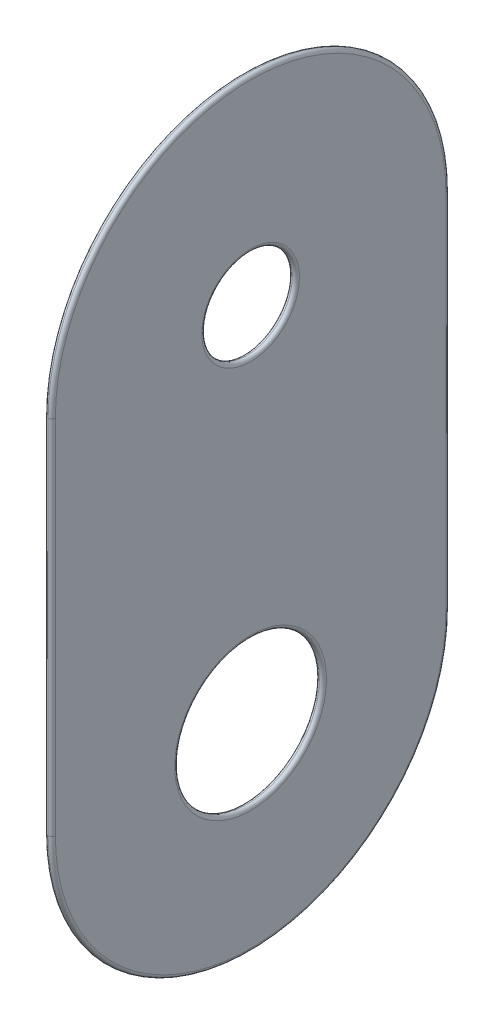
SolidWorks part; units mm, degrees
ref_plane "Front Plane" through (0, 0, 0) normal (0, 0, 1) x (1, 0, 0)
ref_plane "Top Plane" through (0, 0, 0) normal (0, 1, 0) x (1, 0, 0)
ref_plane "Right Plane" through (0, 0, 0) normal (1, 0, 0) x (0, 0, -1)
sketch "Sketch2" plane through (0, 0, 0) normal (1, 0, 0) x (0, 0, -1)
  line L0 (-31.7681, 0) -> (28.4393, 0) construction
  line L1 (0, 26.594) -> (0, -23.9889) construction
  line L2 (0, 12.7) -> (0, -12.7) construction
  line L3 (13.97, 12.7) -> (13.97, -12.7)
  line L4 (-13.97, 12.7) -> (-13.97, -12.7)
  circle A0 centre (0, 12.7) radius 3.175
  circle A1 centre (0, -12.7) radius 5.08
  arc A2 (13.97, 12.7) -> (-13.97, 12.7) centre (0, 12.7) ccw
  arc A3 (-13.97, -12.7) -> (13.97, -12.7) centre (0, -12.7) ccw
  point P9 (0, 0)
  dimension "D2" = 6.35
  dimension "D3" = 10.16
  dimension "D1" = 25.4
  dimension "D4" = 27.94
extrude "Boss-Extrude1" add sketch "Sketch2" along normal mid plane 0.508
fillet "Fillet1" radius 0.254 6 edges at (0.254, -12.7, -5.08) (0.254, 0, -13.97) (0.254, -26.67, 0) (0.254, 0, 13.97) (0.254, 26.67, 0) (0.254, 12.7, -3.175)
fillet "Fillet2" radius 0.254 6 edges at (-0.254, -12.7, -5.08) (-0.254, 12.7, -3.175) (-0.254, 0, 13.97) (-0.254, -26.67, 0) (-0.254, 0, -13.97) (-0.254, 26.67, 0)
